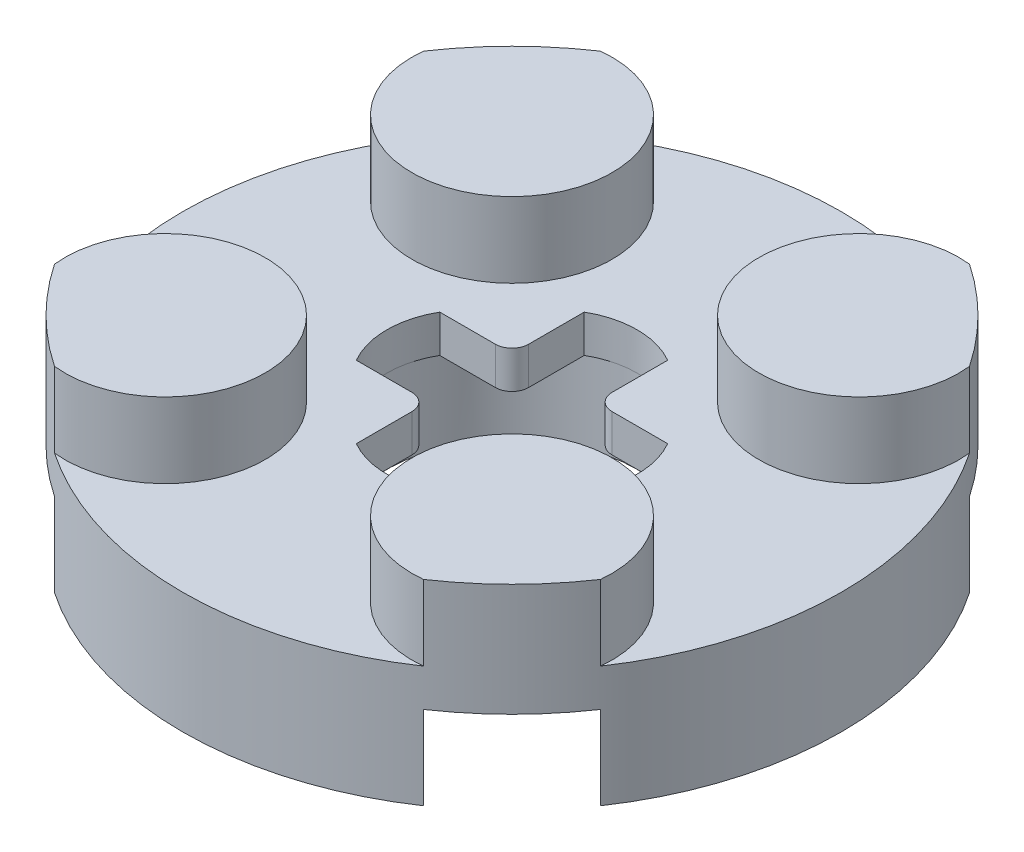
SolidWorks part; units mm, degrees
material "ABS"
ref_plane "Front Plane" through (0, 0, 0) normal (0, 0, 1) x (1, 0, 0)
ref_plane "Top Plane" through (0, 0, 0) normal (0, 1, 0) x (1, 0, 0)
ref_plane "Right Plane" through (0, 0, 0) normal (1, 0, 0) x (0, 0, -1)
sketch "Sketch1" plane through (0, 0, 0) normal (0, 1, 0) x (1, 0, 0)
  circle A0 centre (0, 0) radius 7.9
  dimension "D1" = 15.8
extrude "Boss-Extrude1" add sketch "Sketch1" along normal blind 0.9
sketch "Sketch2" plane through (0, 0.9, 0) normal (0, 1, 0) x (1, 0, 0)
  line L0 (-1.4, -1) -> (-2.7321, -1)
  line L2 (-2.7321, 1) -> (-1.4, 1)
  line L3 (-1, 1.4) -> (-1, 2.7321)
  line L5 (1, 2.7321) -> (1, 1.4)
  line L6 (1.4, 1) -> (2.7321, 1)
  line L8 (2.7321, -1) -> (1.4, -1)
  line L9 (1, -1.4) -> (1, -2.7321)
  line L11 (-1, -2.7321) -> (-1, -1.4)
  arc A0 (1.4, 1) -> (1, 1.4) centre (1.4, 1.4) cw
  arc A1 (1.4, -1) -> (1, -1.4) centre (1.4, -1.4) ccw
  arc A2 (-1, 1.4) -> (-1.4, 1) centre (-1.4, 1.4) cw
  arc A3 (-1, -1.4) -> (-1.4, -1) centre (-1.4, -1.4) ccw
  arc A4 (1, -2.7321) -> (-1, -2.7321) centre (0, -1) cw
  arc A5 (-2.7321, -1) -> (-2.7321, 1) centre (-1, 0) cw
  arc A6 (-1, 2.7321) -> (1, 2.7321) centre (0, 1) cw
  arc A7 (2.7321, -1) -> (2.7321, 1) centre (1, 0) ccw
  point P15 (-3, 0)
  point P28 (3, 0)
  point P30 (0, 3)
  point P31 (0, -3)
  dimension "D2" = 0.4
  dimension "D3" = 2
  dimension "D1" = 2
  dimension "D4" = 2
  dimension "D5" = 6
extrude "Cut-Extrude1" cut sketch "Sketch2" against normal through all both and the other way through all
sketch "Sketch3" plane through (0, 0.9, 0) normal (0, 1, 0) x (1, 0, 0)
  line L0 (0, 0) -> (5.4845, 5.4845) construction
  line L1 (5.4845, 5.4845) -> (-5.5861, -5.5861) construction
  line L2 (0, 0) -> (-5.5861, 5.5861) construction
  line L3 (-5.5861, 5.5861) -> (5.5861, -5.5861) construction
  circle A0 centre (0, 0) radius 7.9 construction
  arc A1 (4.4239, 6.5452) -> (6.5452, 4.4239) centre (4.1598, 4.1598) ccw
  arc A2 (4.4239, 6.5452) -> (6.5452, 4.4239) centre (0, 0) cw
  dimension "D1" = 2.4
  dimension "D3" = 7.9
  dimension "D2" = 3
extrude "Boss-Extrude2" add sketch "Sketch3" along normal blind 1.8
pattern_circular "CirPattern1" count 4 over 360 about axis through (0, 0.9, 0) along (0, 1, 0) of "Boss-Extrude2"
sketch "Sketch4" plane through (0, 0, 0) normal (0, -1, 0) x (1, 0, 0)
  circle A0 centre (0, 0) radius 3
  arc A2 (1, 2.7321) -> (-1, 2.7321) centre (0, 1) ccw construction
  circle A3 centre (0, 0) radius 3.6
  point P7 (0, 3)
  dimension "D1" = 0.6
extrude "Boss-Extrude5" add sketch "Sketch4" along normal blind 2
ref_axis "Axis1" through (-6.5452, 2.7, -4.4239) along (0, -1, 0)
ref_axis "Axis2" through (-6.5452, 2.7, 4.4239) along (0, -1, 0)
sketch "Sketch6" plane through (0, 0, 0) normal (0, -1, 0) x (1, 0, 0)
  line L0 (-6.5452, -4.4239) -> (-6.5452, 4.4239)
  arc A0 (-6.5452, -4.4239) -> (-6.5452, 4.4239) centre (0, 0) cw
  circle A1 centre (0, 0) radius 7.9 construction
  dimension "D1" = 7.9
extrude "Boss-Extrude6" add sketch "Sketch6" along normal blind 2
pattern_circular "CirPattern2" count 4 over 360 about axis through (0, 0, 0) along (0, 1, 0) of "Boss-Extrude6"
sketch "Sketch7" plane through (0, 0, 0) normal (0, -1, 0) x (1, 0, 0)
  circle A0 centre (-4.4239, -4.4239) radius 1.3
  dimension "D1" = 2.6
extrude "Cut-Extrude2" cut sketch "Sketch7" against normal blind 1.7
pattern_circular "CirPattern3" count 4 over 360 about axis through (0, 0, 0) along (0, 1, 0) of "Cut-Extrude2"
